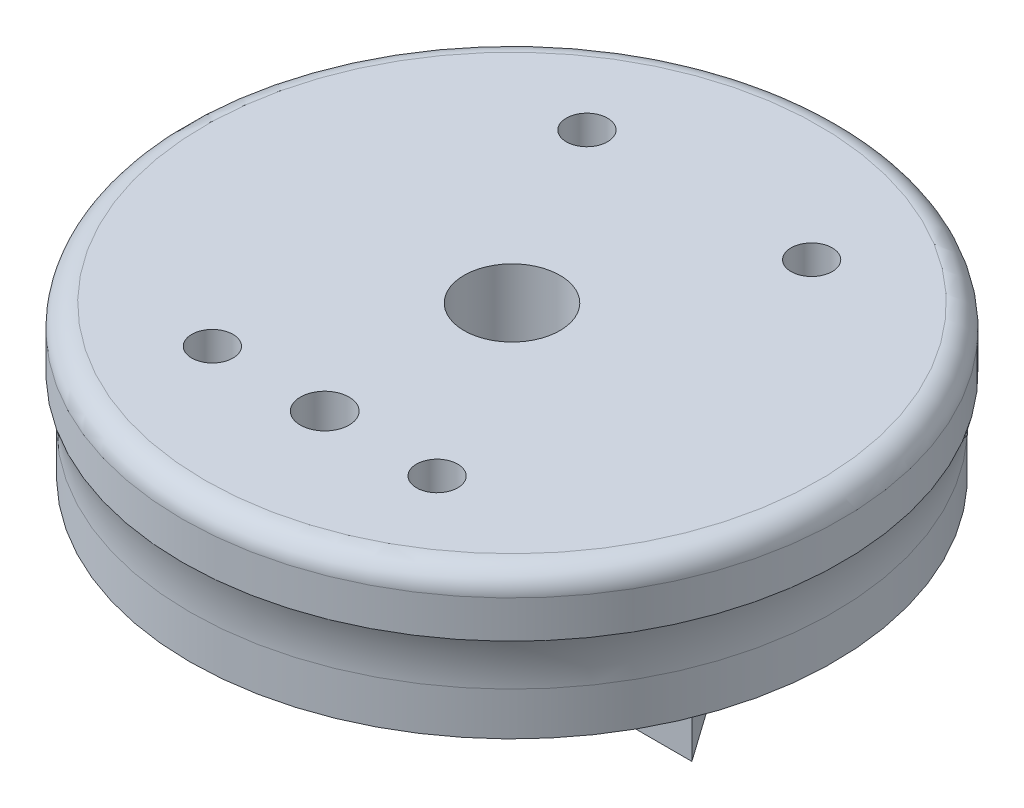
SolidWorks part; units mm, degrees
ref_plane "Front Plane" through (0, 0, 0) normal (0, 0, 1) x (1, 0, 0)
ref_plane "Top Plane" through (0, 0, 0) normal (0, 1, 0) x (1, 0, 0)
ref_plane "Right Plane" through (0, 0, 0) normal (1, 0, 0) x (0, 0, -1)
sketch "Sketch1" plane through (0, 0, 0) normal (0, 1, 0) x (1, 0, 0)
  circle A0 centre (0, 0) radius 43
  dimension "D1" = 86
extrude "Boss-Extrude1" add sketch "Sketch1" along normal blind 20
sketch "Sketch2" plane through (0, 20, 0) normal (0, 1, 0) x (1, 0, 0)
  circle A0 centre (0, 0) radius 44
  dimension "D1" = 88
extrude "Boss-Extrude2" add sketch "Sketch2" against normal blind 8
fillet "Fillet1" radius 20 1 edges at (0, 12, 43)
sketch "Sketch3" plane through (0, 20, 0) normal (0, 1, 0) x (1, 0, 0)
  line L0 (0, 0) -> (-19.6691, 27.8465) construction
  circle A0 centre (-9.2225, 13.0567) radius 12.1462 construction
  point P2 (0, 0)
sketch "Sketch4" plane through (0, 0, 0) normal (0, -1, 0) x (1, 0, 0)
  line L0 (28.8901, 11) -> (35.0116, 11) construction
  line L1 (-2.0464, -32.7984) -> (28.8901, 11) construction
  line L2 (0, -38.5677) -> (-2.0464, -32.7984) construction
  line L3 (35.0116, 11) -> (0, -38.5677) construction
  line L4 (28.8901, 11) -> (35.0116, 11)
  line L5 (-2.0464, -32.7984) -> (28.8901, 11)
  line L6 (0, -38.5677) -> (-2.0464, -32.7984)
  line L7 (35.0116, 11) -> (0, -38.5677)
extrude "Boss-Extrude3" add sketch "Sketch4" along normal blind 10
sketch "Sketch5" plane through (18.1744, 0, -12.8373) normal (0.8168, 0, -0.5769) x (-0.5769, 0, -0.8168)
  line L0 (31.5018, -10) -> (-29.184, -10) construction
  line L1 (-29.184, -10) -> (-29.184, 0) construction
  line L2 (31.5018, -10) -> (31.5018, 0) construction
  circle A0 centre (-21.184, -5) radius 2.1
  circle A1 centre (23.5018, -5) radius 2.1
  dimension "D3" = 4.2
  dimension "D4" = 8
  dimension "D1" = 5
  dimension "D2" = 8
extrude "Cut-Extrude1" cut sketch "Sketch5" against normal blind 4
sketch "Sketch7" plane through (0, 0, 0) normal (0, -1, 0) x (1, 0, 0)
  line L103 (8.456, -5.84) -> (-5.1518, 3.7717)
  line L104 (-0.1147, -25.4965) -> (9.4969, -11.8887)
  line L105 (-19.7713, -16.9258) -> (-6.1635, -26.5375)
  line L106 (-11.2006, 2.7307) -> (-20.8123, -10.877)
  arc A24 (-5.1518, 3.7717) -> (-11.2006, 2.7307) centre (-7.6557, 0.2268) ccw
  arc A25 (9.4969, -11.8887) -> (8.456, -5.84) centre (5.9521, -9.3849) ccw
  arc A26 (-6.1635, -26.5375) -> (-0.1147, -25.4965) centre (-3.6596, -22.9926) ccw
  arc A27 (-20.8123, -10.877) -> (-19.7713, -16.9258) centre (-17.2674, -13.3809) ccw
extrude "Cut-Extrude2" cut sketch "Sketch7" against normal blind 5
fillet "Fillet2" radius 3 1 edges at (0, 20, 44)
sketch "Sketch8" plane through (0, 0, 0) normal (0, -1, 0) x (1, 0, 0)
  line L0 (28.8901, 11) -> (-35.0116, 11)
  line L1 (28.8901, 11) -> (25.3584, 6)
  line L2 (28.8901, 11) -> (-2.0464, -32.7984) construction
  line L4 (25.3584, 6) -> (-31.4799, 6)
  line L5 (-3.0608, 11) -> (-3.0608, 2.8896) construction
  line L6 (-35.0116, 11) -> (-31.4799, 6)
  dimension "D1" = 5
extrude "Boss-Extrude4" add sketch "Sketch8" along normal blind 10
sketch "Sketch10" plane through (0, 0, 11) normal (0, 0, 1) x (1, 0, 0)
  line L0 (35.0116, -10) -> (-35.0116, -10) construction
  line L1 (-35.0116, -10) -> (-35.0116, 0) construction
  line L2 (35.0116, -10) -> (35.0116, 0) construction
  circle A0 centre (-17.0116, -5) radius 2.1
  circle A1 centre (17.0116, -5) radius 2.1
  dimension "D1" = 4.2
  dimension "D4" = 4.2
  dimension "D2" = 5
  dimension "D3" = 18
  dimension "D5" = 5
  dimension "D6" = 18
extrude "Cut-Extrude3" cut sketch "Sketch10" against normal blind 4
sketch "Sketch11" plane through (0, 0, 0) normal (0, -1, 0) x (1, 0, 0)
  circle A0 centre (0, 25) radius 3.25
  dimension "D1" = 6.5
  dimension "D2" = 25
extrude "Cut-Extrude4" cut sketch "Sketch11" against normal blind 47
sketch "Croquis1" plane through (0, 20, 0) normal (0, 1, 0) x (1, 0, 0)
  line L0 (-15, 25) -> (-15, -25) construction
  line L1 (-15, 25) -> (15, 25) construction
  line L2 (-15, -25) -> (15, -25) construction
  line L3 (15, 25) -> (15, -25) construction
  line L4 (-15, 25) -> (15, -25) construction
  line L5 (-15, -25) -> (15, 25) construction
  circle A0 centre (-15, 25) radius 2.75
  circle A1 centre (15, 25) radius 2.75
  circle A2 centre (15, -25) radius 2.75
  circle A3 centre (-15, -25) radius 2.75
  point P1 (0, 0)
  dimension "D3" = 5.5
  dimension "D1" = 50
  dimension "D2" = 30
extrude "Cortar-Extruir1" cut sketch "Croquis1" against normal blind 13
sketch "Croquis2" plane through (0, 20, 0) normal (0, 1, 0) x (1, 0, 0)
  circle A0 centre (0, 0) radius 6.4
  dimension "D1" = 12.8
extrude "Cortar-Extruir2" cut sketch "Croquis2" against normal blind 10
